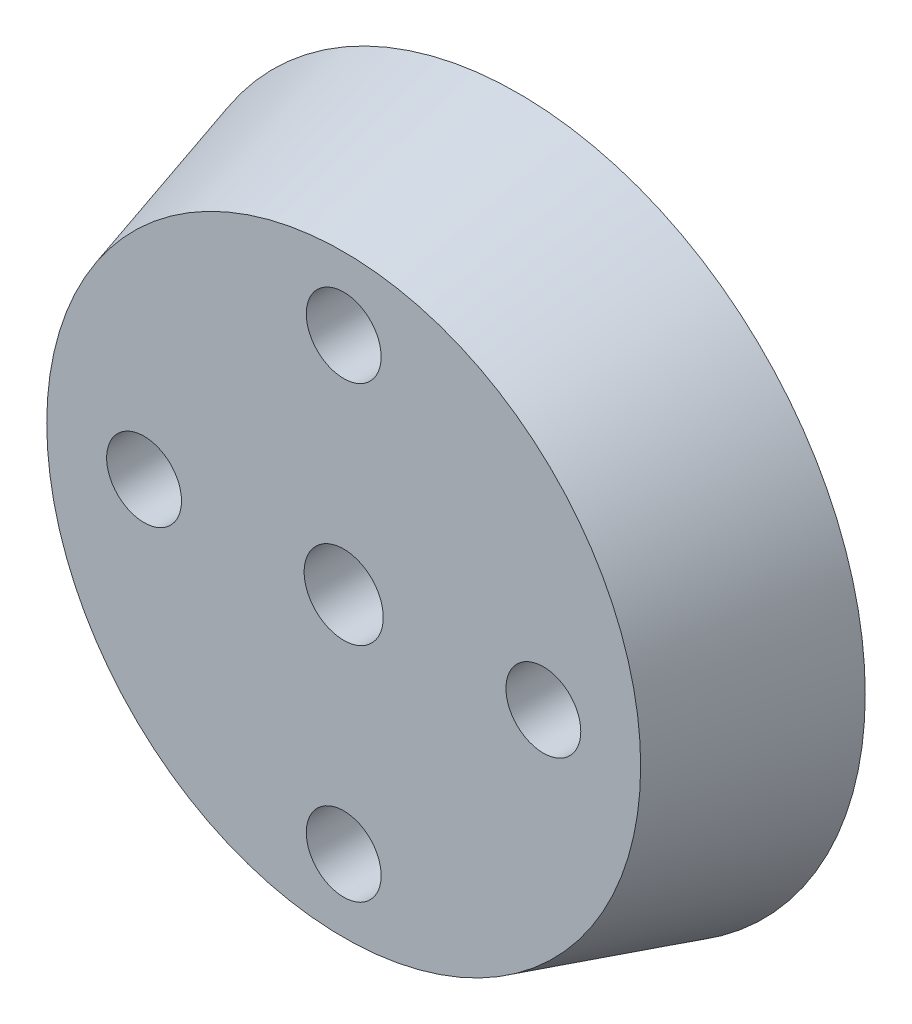
SolidWorks part; units mm, degrees
ref_plane "Front Plane" through (0, 0, 0) normal (0, 0, 1) x (1, 0, 0)
ref_plane "Top Plane" through (0, 0, 0) normal (0, 1, 0) x (1, 0, 0)
ref_plane "Right Plane" through (0, 0, 0) normal (1, 0, 0) x (0, 0, -1)
sketch "Sketch1" plane through (0, 0, 0) normal (0, 0, 1) x (1, 0, 0)
  circle A0 centre (0, 0) radius 13.9
  dimension "D1" = 27.8
extrude "Boss-Extrude1" add sketch "Sketch1" along normal blind 7 contours A0
sketch "Sketch2" plane through (0, 0, 7) normal (0, 0, 1) x (1, 0, 0)
  circle A0 centre (0, 0) radius 1.585
  dimension "D1" = 3.17
extrude "Cut-Extrude1" cut sketch "Sketch2" against normal up to next
sketch "Sketch3" plane through (0, 0, 7) normal (0, 0, 1) x (1, 0, 0)
  circle A0 centre (0, 0) radius 8 construction
  circle A1 centre (0, 0) radius 9 construction
  circle A2 centre (-8, 0) radius 1.5
  circle A3 centre (8, 0) radius 1.5
  circle A4 centre (0, -9) radius 1.5
  circle A5 centre (0, 9) radius 1.5
  dimension "D1" = 3
  dimension "D2" = 3
  dimension "D3" = 3
  dimension "D4" = 3
extrude "Cut-Extrude2" cut sketch "Sketch3" against normal up to next
chamfer "Chamfer1" distance 7 distance2 2 1 edges at (13.9, 0, 7) first distance on face at (13.9, 0, 7)
